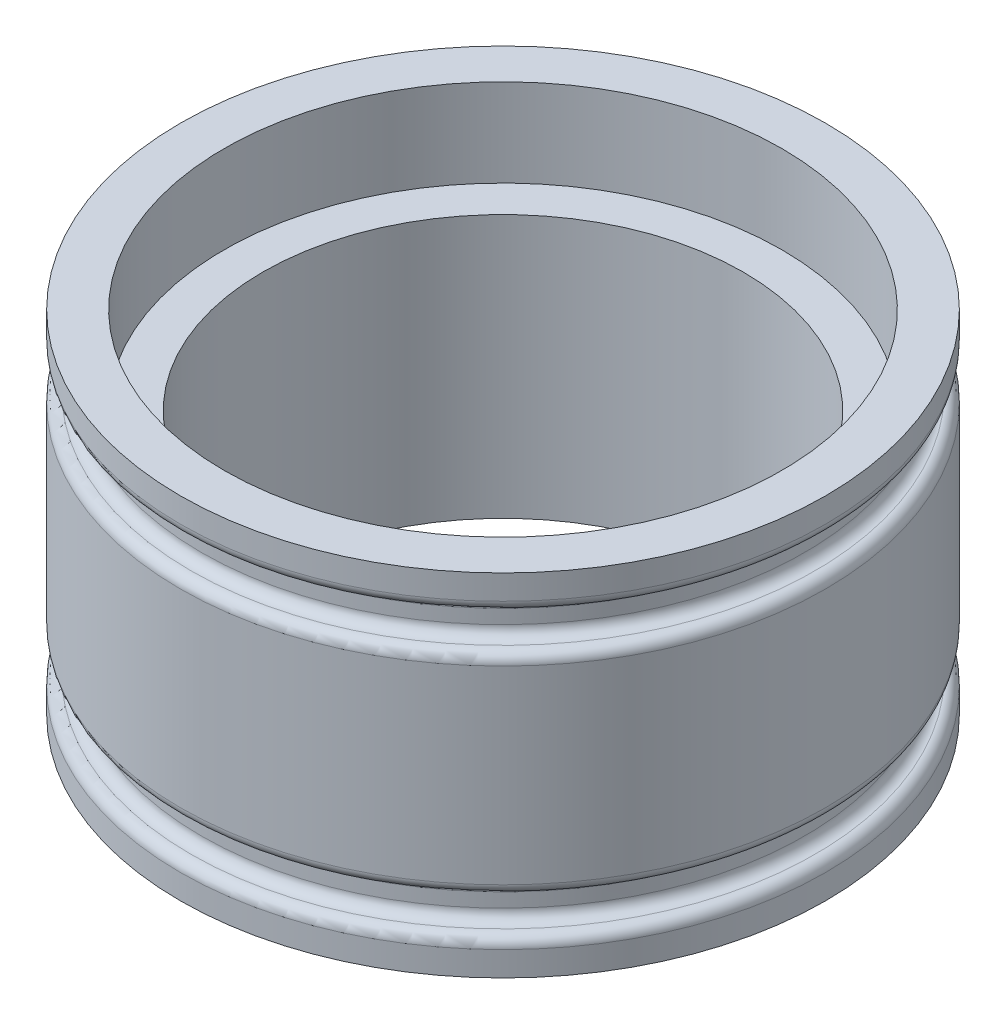
SolidWorks part; units mm, degrees
ref_plane "Front Plane" through (0, 0, 0) normal (0, 0, 1) x (1, 0, 0)
ref_plane "Top Plane" through (0, 0, 0) normal (0, 1, 0) x (1, 0, 0)
ref_plane "Right Plane" through (0, 0, 0) normal (1, 0, 0) x (0, 0, -1)
sketch "Sketch2" plane through (0, 0, 0) normal (0, 1, 0) x (1, 0, 0)
  line L0 (0, 20.193) -> (0, 23.368) construction
  circle A0 centre (0, 0) radius 20.193
  circle A1 centre (0, 0) radius 23.368
  dimension "D1" = 40.386
  dimension "D2" = 3.175
extrude "Boss-Extrude1" add sketch "Sketch2" along normal blind 25.4
sketch "Sketch3" plane through (0, 0, 0) normal (0, -1, 0) x (1, 0, 0)
  circle A0 centre (0, 0) radius 17.399
  circle A1 centre (0, 0) radius 20.193 construction
  circle A2 centre (0, 0) radius 20.193
  dimension "D1" = 34.798
extrude "Boss-Extrude2" add sketch "Sketch3" against normal offset from surface (19.05 mm away) 6.35 up to face at (0, 25.4, 23.368)
sketch "Sketch4" plane through (0, 0, 0) normal (0, 0, 1) x (1, 0, 0)
  line L0 (-23.368, 25.4) -> (-23.368, 0) construction
  line L5 (-23.368, 12.7) -> (49976.632, 12.7) construction
  line L6 (-23.368, 5.08) -> (-21.844, 5.08)
  line L7 (-23.368, 5.08) -> (-23.368, 2.54)
  line L8 (-23.368, 2.54) -> (-21.844, 2.54)
  line L9 (-21.844, 5.08) -> (-21.844, 2.54)
  line L10 (-21.844, 20.32) -> (-21.844, 22.86)
  line L11 (-23.368, 22.86) -> (-21.844, 22.86)
  line L12 (-23.368, 20.32) -> (-23.368, 22.86)
  line L13 (-23.368, 20.32) -> (-21.844, 20.32)
  line L14 (-23.368, 0) -> (23.368, 0) construction
  line L15 (0, 0) -> (0, -50000) construction
  point P12 (-23.368, 12.7)
  dimension "D1" = 2.54
  dimension "D2" = 1.524
  dimension "D3" = 2.54
revolve "Cut-Revolve1" cut sketch "Sketch4" angle 360 about L15
fillet "Fillet1" radius 0.762 8 edges at (0, 2.54, 21.844) (0, 5.08, 21.844) (0, 5.08, 23.368) (0, 2.54, 23.368) (0, 20.32, 23.368) (0, 20.32, 21.844) (0, 22.86, 21.844) (0, 22.86, 23.368)
